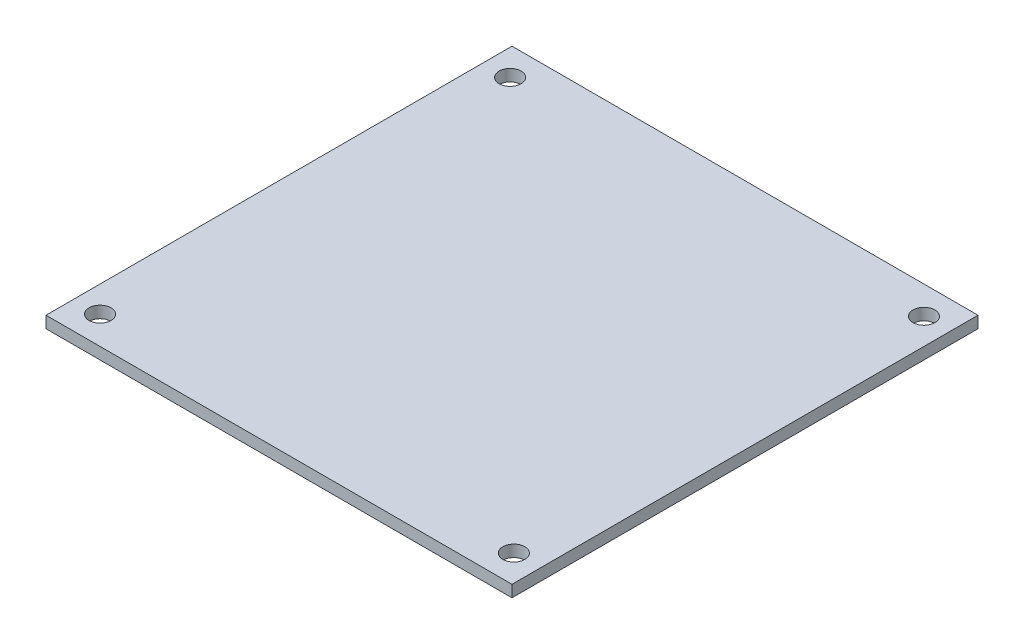
SolidWorks part; units mm, degrees
ref_plane "Front Plane" through (0, 0, 0) normal (0, 0, 1) x (1, 0, 0)
ref_plane "Top Plane" through (0, 0, 0) normal (0, 1, 0) x (1, 0, 0)
ref_plane "Right Plane" through (0, 0, 0) normal (1, 0, 0) x (0, 0, -1)
sketch "Sketch1" plane through (0, 0, 0) normal (0, 1, 0) x (1, 0, 0)
  line L0 (31.75, 0) -> (-31.75, 0) construction
  line L1 (31.75, -31.75) -> (-31.75, -31.75)
  line L2 (31.75, -31.75) -> (31.75, 31.75)
  line L3 (31.75, 31.75) -> (-31.75, 31.75)
  line L4 (-31.75, -31.75) -> (-31.75, 31.75)
  line L5 (31.75, -31.75) -> (-31.75, 31.75) construction
  line L6 (31.75, 31.75) -> (-31.75, -31.75) construction
  line L7 (0, -31.75) -> (0, 31.75) construction
  line L8 (-28.194, 27.94) -> (28.194, 27.94) construction
  circle A0 centre (-28.194, 27.94) radius 1.5
  circle A1 centre (28.194, 27.94) radius 1.5
  circle A2 centre (28.194, -27.94) radius 1.5
  circle A3 centre (-28.194, -27.94) radius 1.5
  point P0 (0, 0)
  point P9 (0, 0)
  point P12 (0, 0)
  point P14 (0, 27.94)
  point P16 (28.194, 27.94)
  dimension "D5" = 3
  dimension "D1" = 63.5
  dimension "D2" = 63.5
  dimension "D3" = 56.388
  dimension "D4" = 3.81
extrude "Boss-Extrude1" add sketch "Sketch1" along normal blind 1.6
